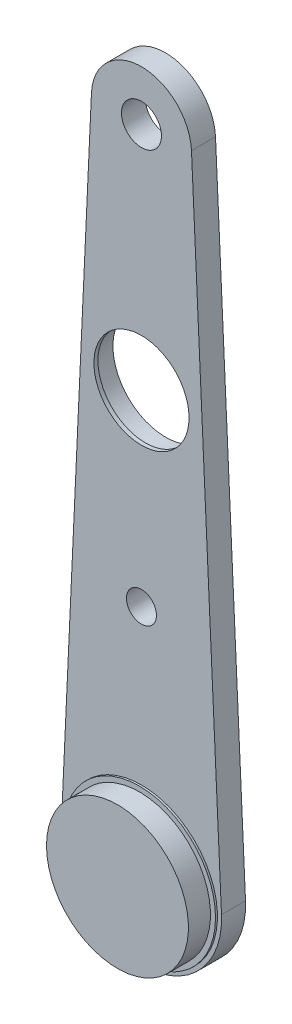
SolidWorks part; units mm, degrees
ref_plane "Front Plane" through (0, 0, 0) normal (0, 0, 1) x (1, 0, 0)
ref_plane "Top Plane" through (0, 0, 0) normal (0, 1, 0) x (1, 0, 0)
ref_plane "Right Plane" through (0, 0, 0) normal (1, 0, 0) x (0, 0, -1)
sketch "Sketch1" plane through (0, 0, 0) normal (0, 0, 1) x (1, 0, 0)
  line L0 (0, 205.4835) -> (0, 0) construction
  line L1 (25.3727, 1.1774) -> (15.8579, 206.2193)
  line L2 (-15.8579, 206.2193) -> (-25.3727, 1.1774)
  circle A1 centre (0, 205.4835) radius 6.35
  arc A2 (-15.8579, 206.2193) -> (15.8579, 206.2193) centre (0, 205.4835) cw
  arc A3 (-25.3727, 1.1774) -> (25.3727, 1.1774) centre (0, 0) ccw
  dimension "D2" = 15.875
  dimension "D3" = 25.4
  dimension "D4" = 12.7
  dimension "D1" = 205.4835
extrude "Boss-Extrude1" add sketch "Sketch1" along normal mid plane 7.62
sketch "Sketch2" plane through (0, 0, 3.81) normal (0, 0, 1) x (1, 0, 0)
  circle A0 centre (0, 0) radius 22.5
  dimension "D1" = 45
extrude "Boss-Extrude2" add sketch "Sketch2" along normal blind 7.62
sketch "Sketch3" plane through (0, 0, 3.81) normal (0, 0, 1) x (1, 0, 0)
  circle A0 centre (0, 0) radius 24.0899
extrude "Boss-Extrude3" add sketch "Sketch3" along normal offset from surface (0.62 mm away) 7 up to face at (22.5, 0, 11.43)
sketch "Sketch4" plane through (0, 0, 3.81) normal (0, 0, 1) x (1, 0, 0)
  circle A0 centre (0, 73.0199) radius 4.7625
  circle A1 centre (0, 132.4635) radius 16.6688
  circle A2 centre (0, 205.4835) radius 6.35 construction
  dimension "D2" = 9.525
  dimension "D3" = 33.3375
  dimension "D1" = 73.0199
  dimension "D4" = 73.0199
extrude "Cut-Extrude1" cut sketch "Sketch4" against normal through all both and the other way through all
sketch "Sketch5" plane through (0, 0, 0) normal (0, 0, 1) x (1, 0, 0)
  line L0 (-155.5635, 72.3706) -> (0, 227.9341)
  line L1 (-155.5635, 72.3706) -> (0, -83.1929)
  line L2 (0, 227.9341) -> (155.5635, 72.3706)
  line L3 (0, -83.1929) -> (155.5635, 72.3706)
  line L4 (-155.5635, 72.3706) -> (155.5635, 72.3706) construction
  line L5 (0, 227.9341) -> (0, -83.1929) construction
  arc A1 (15.8579, 206.2193) -> (-15.8579, 206.2193) centre (0, 205.4835) ccw construction
  point P1 (0, 72.3706)
  dimension "D1" = 220
sketch "Sketch6" plane through (0, 0, 3.81) normal (0, 0, 1) x (1, 0, 0)
  circle A0 centre (0, 132.4635) radius 16.6688
  circle A1 centre (0, 132.4635) radius 15.0813
  circle A2 centre (0, 132.4635) radius 16.6688 construction
  dimension "D1" = 1.5875
extrude "Boss-Extrude4" add sketch "Sketch6" against normal offset from surface (1.27 mm away) 6.35 up to face at (4.7625, 73.0199, -3.81)
equation "\"UpperLinkLength\"= \"LowerFirstStage\" + \"LowerSecondStage\""
equation "\"LowerFirstStage\"= \"60T_20T_171B\""
equation "\"LowerSecondStage\"= \"60T_20T_113B\""
equation "\"D1@Sketch1\"=\"UpperLinkLength\""
equation "\"UpperStage\"= \"60T_20T_113B\""
equation "\"60T_20T_113B\"= 2.8748"
equation "\"60T_20T_171B\"= 5.2151"
equation "\"D1@Sketch4\"=\"UpperStage\""
equation "\"D4@Sketch4\"=\"LowerSecondStage\""
